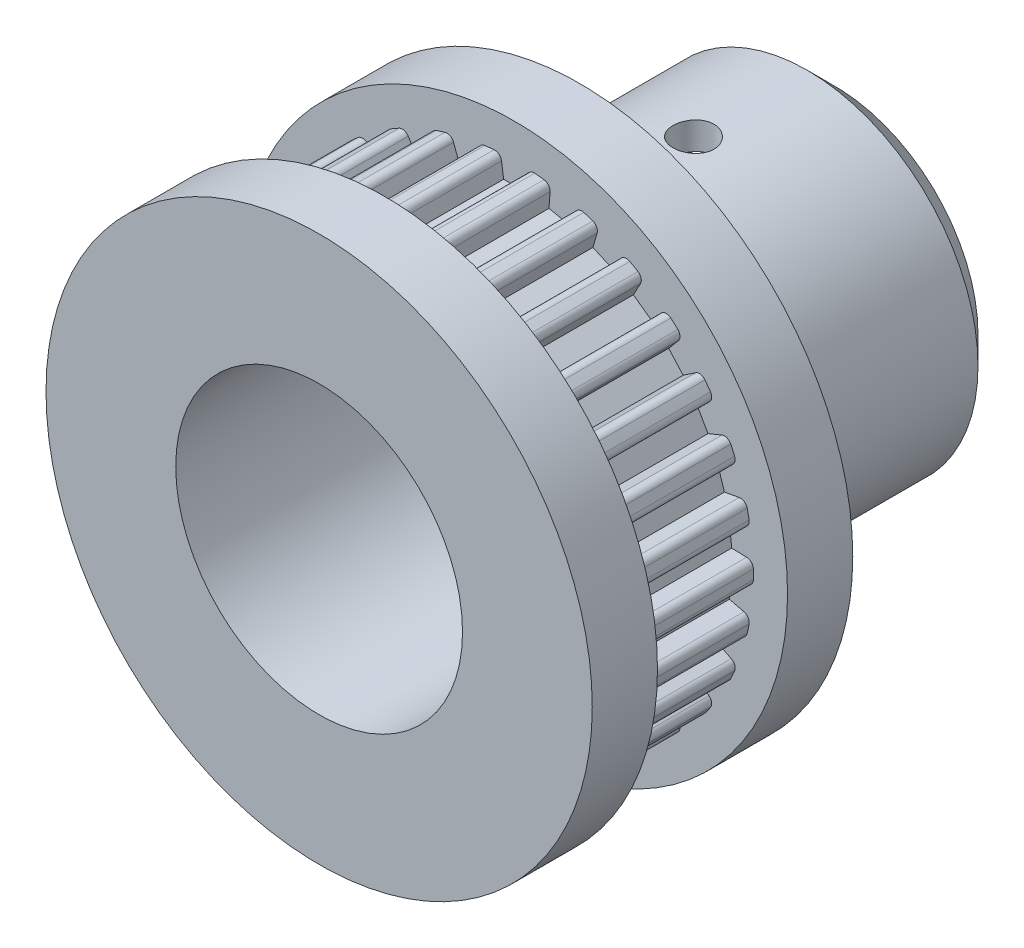
SolidWorks part; units mm, degrees
ref_plane "Front Plane" through (0, 0, 0) normal (0, 0, 1) x (1, 0, 0)
ref_plane "Top Plane" through (0, 0, 0) normal (0, 1, 0) x (1, 0, 0)
ref_plane "Right Plane" through (0, 0, 0) normal (1, 0, 0) x (0, 0, -1)
sketch "Sketch3" plane through (0, 0, 0) normal (0, 0, 1) x (1, 0, 0)
  circle A0 centre (0, 0) radius 17.5
  dimension "D1" = 35
extrude "Boss-Extrude1" add sketch "Sketch3" along normal blind 9.525 contours A0
sketch "Sketch4" plane through (0, 0, 0) normal (0, 0, -1) x (-1, 0, 0)
  line L0 (-1.5875, 21.7403) -> (1.5875, 21.7403)
  line L1 (1.5875, 21.7403) -> (0.7937, 15.9125)
  line L2 (0.7937, 15.9125) -> (-0.7937, 15.9125)
  line L3 (-0.7937, 15.9125) -> (-1.5875, 21.7403)
  circle A0 centre (0, 0) radius 17.5 construction
  point P2 (0, 15.9125)
  point P6 (0, 17.5)
  circle M5 centre (0, 0) radius 17.5
  dimension "D1" = 3.175
  dimension "D2" = 1.5875
  dimension "D3" = 1.5875
  dimension "D4" = 5.8278
extrude "Cut-Extrude1" cut sketch "Sketch4" against normal blind 9.525 contours L3 L1 L0 M5 | L3 L0 L1 L2 region at (0, 19.7732, 0)
fillet "Fillet1" radius 0.508 1 edges at (1.006, 17.4711, 4.7625)
fillet "Fillet2" radius 0.508 1 edges at (-1.006, 17.4711, 4.7625)
sketch "Sketch5" plane through (0, 0, 9.525) normal (0, 0, 1) x (1, 0, 0)
  circle A0 centre (0, 0) radius 20
  dimension "D1" = 40
extrude "Boss-Extrude2" add sketch "Sketch5" along normal blind 4.7752
pattern_circular "CirPattern1" count 30 over 360 about axis through (0, 0, 0) along (0, 0, 1) of "Cut-Extrude1", "Fillet1", "Fillet2"
sketch "Sketch7" plane through (0, 0, 0) normal (0, 0, -1) x (-1, 0, 0)
  circle A0 centre (0, 0) radius 20
  dimension "D1" = 40
extrude "Boss-Extrude3" add sketch "Sketch7" along normal blind 4.7752
sketch "Sketch8" plane through (0, 0, -4.7752) normal (0, 0, -1) x (-1, 0, 0)
  circle A0 centre (0, 0) radius 12.5
  dimension "D1" = 25
extrude "Boss-Extrude5" add sketch "Sketch8" along normal blind 19.05
sketch "Sketch12" plane through (0, 0, -23.8252) normal (0, 0, -1) x (-1, 0, 0)
  circle A0 centre (0, 0) radius 10.5
  dimension "D1" = 21
extrude "Cut-Extrude3" cut sketch "Sketch12" against normal through all
chamfer "Chamfer1" distance 2.38 1 edges at (-12.5, 0, -23.8252)
sketch "Sketch13" plane through (0, 0, 0) normal (0, 1, 0) x (1, 0, 0)
  line L3 (0, 21.4452) -> (0, 4.7752) construction
  line L4 (-12.5, 21.4452) -> (12.5, 21.4452) construction
  line L5 (20, 4.7752) -> (-20, 4.7752) construction
  circle A0 centre (0, 13.1102) radius 1.5
  point P9 (0, 0)
  point P10 (0, 13.1102)
  dimension "D1" = 3
extrude "Cut-Extrude4" cut sketch "Sketch13" against normal blind 1.27 and the other way through all
